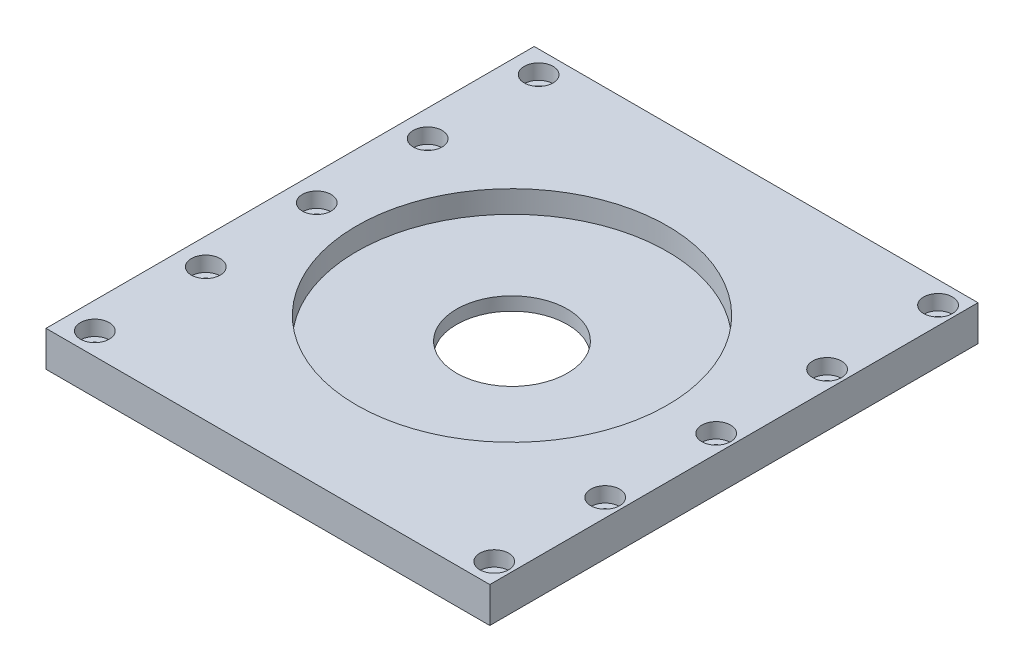
SolidWorks part; units mm, degrees
material "6061-T6 (SS)"
ref_plane "Front Plane" through (0, 0, 0) normal (0, 0, 1) x (1, 0, 0)
ref_plane "Top Plane" through (0, 0, 0) normal (0, 1, 0) x (1, 0, 0)
ref_plane "Right Plane" through (0, 0, 0) normal (1, 0, 0) x (0, 0, -1)
sketch "Sketch1" plane through (0, 0, 0) normal (0, 1, 0) x (1, 0, 0)
  line L1 (0, 0) -> (100, 0)
  line L2 (0, 0) -> (0, 110)
  line L3 (0, 110) -> (100, 110)
  line L4 (100, 0) -> (100, 110)
  dimension "D1" = 110
  dimension "D2" = 100
extrude "Boss-Extrude1" add sketch "Sketch1" along normal blind 8
sketch "Sketch2" plane through (0, 8, 0) normal (0, 1, 0) x (1, 0, 0)
  line L0 (0, 110) -> (6, 110)
  line L1 (100, 110) -> (0, 110) construction
  line L2 (6, 110) -> (6, 0)
  line L3 (0, 0) -> (100, 0) construction
  line L4 (0, 110) -> (0, 0) construction
  line L5 (96, 110) -> (96, 0) construction
  line L7 (100, 0) -> (100, 110) construction
  line L8 (0, 55) -> (6, 55) construction
  point P11 (6, 105)
  point P18 (6, 80)
  point P19 (6, 55)
  point P20 (6, 30)
  point P21 (6, 5)
  point P32 (96, 55)
  point P41 (96, 30)
  point P42 (96, 5)
  point P43 (96, 55)
  point P44 (96, 30)
  point P45 (96, 80)
  point P46 (96, 55)
  point P47 (96, 80)
  point P48 (96, 105)
  dimension "D1" = 5
  dimension "D3" = 6
  dimension "D4" = 4
  dimension "D5" = 3
  dimension "D6" = 3
hole_wizard "CBORE for M3 Hex Socket Head Cap Screw1" positions "Sketch2" profile "Sketch3" counterbore size "M3" standard "DIN"
sketch "Sketch3" plane through (96, 8, -105) normal (1, 0, 0) x (0, 0, 1)
  line L0 (0, 0) -> (0, 9.0215)
  line L1 (0, 9.0215) -> (1.7, 8)
  line L2 (1.7, 8) -> (1.7, 3.4)
  line L3 (1.7, 3.4) -> (3.25, 3.4)
  line L4 (3.25, 3.4) -> (3.25, 0)
  line L5 (3.25, 0) -> (0, 0)
  line L10 (0, 9.0215) -> (-1.7, 8) construction
  line L11 (0, -6.35) -> (0, 107.95) construction
  dimension "Hole Dia." = 3.4
  dimension "Hole Depth" = 8
  dimension "C'Bore Dia." = 6.5
  dimension "C'Bore Depth" = 3.4
  dimension "Drill Angle" = 118
sketch "Sketch6" plane through (0, 8, 0) normal (0, 1, 0) x (1, 0, 0)
  line L2 (100, 110) -> (0, 110) construction
  line L3 (100, 110) -> (0, 0)
  line L4 (0, 0) -> (0, 110)
  line L5 (0, 110) -> (100, 0)
  line L6 (0, 0) -> (100, 0) construction
  point P19 (50, 55)
hole_wizard "Ø25.0mm Dowel Hole1" positions "Sketch6" profile "Sketch5" hole size "Ø25.0" standard "DIN"
sketch "Sketch5" plane through (50, 8, -55) normal (1, 0, 0) x (0, 0, 1)
  line L0 (0, 0) -> (0, 17.5108)
  line L1 (0, 17.5108) -> (12.5, 10)
  line L2 (12.5, 10) -> (12.5, 0)
  line L5 (12.5, 0) -> (0, 0)
  line L10 (0, 17.5108) -> (-12.5, 10) construction
  line L11 (0, -6.35) -> (0, 107.95) construction
  dimension "Hole Dia." = 25
  dimension "Hole Depth" = 10
  dimension "Drill Angle" = 118
sketch "Sketch7" plane through (0, 8, 0) normal (0, 1, 0) x (1, 0, 0)
  circle A0 centre (50, 55) radius 35
  dimension "D1" = 70
extrude "Cut-Extrude1" cut sketch "Sketch7" against normal blind 5
